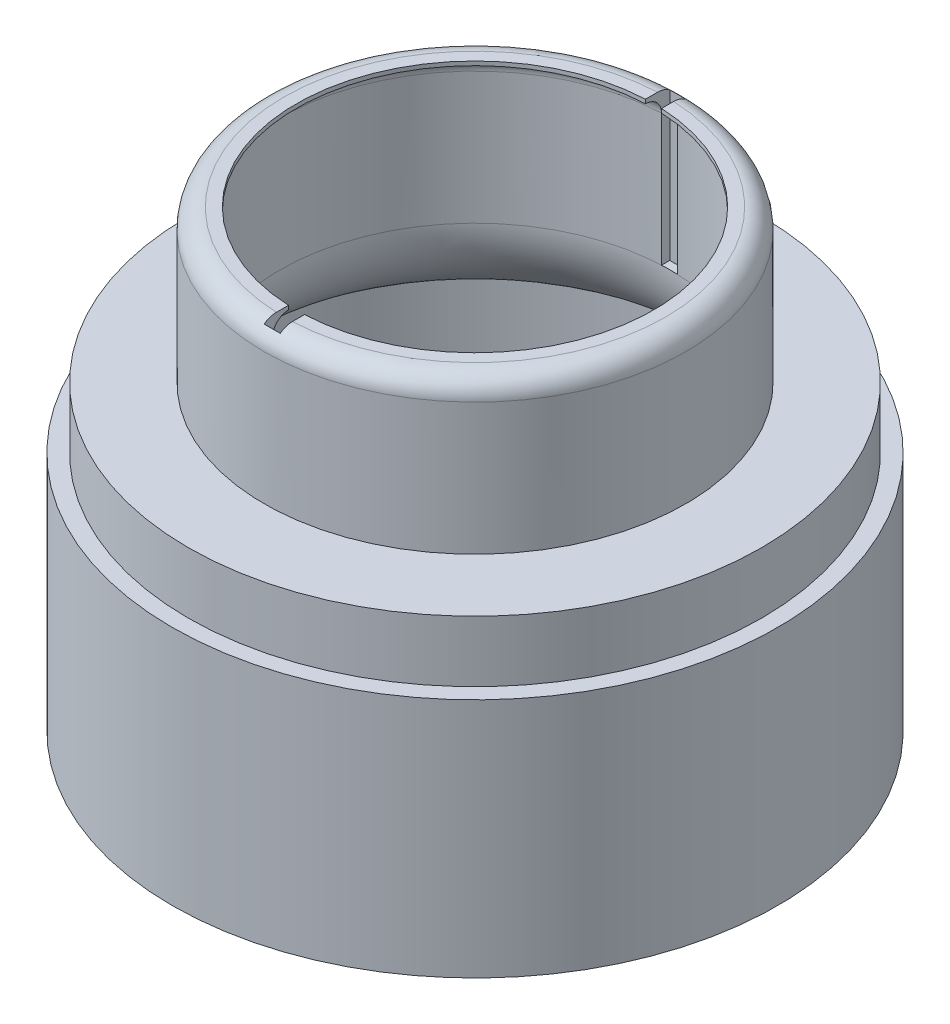
SolidWorks part; units mm, degrees
ref_plane "Front Plane" through (0, 0, 0) normal (0, 0, 1) x (1, 0, 0)
ref_plane "Top Plane" through (0, 0, 0) normal (0, 1, 0) x (1, 0, 0)
ref_plane "Right Plane" through (0, 0, 0) normal (1, 0, 0) x (0, 0, -1)
sketch "Sketch2" plane through (0, 0, 0) normal (0, 1, 0) x (1, 0, 0)
  circle A0 centre (0, 0) radius 18.85
  dimension "D1" = 37.7
extrude "Boss-Extrude1" add sketch "Sketch2" along normal blind 15
sketch "Sketch4" plane through (0, 0, 0) normal (0, -1, 0) x (-1, 0, 0)
  circle A0 centre (0, 0) radius 17.85
  dimension "D1" = 35.7
extrude "Cut-Extrude2" cut sketch "Sketch4" against normal blind 13
sketch "Sketch5" plane through (0, 15, 0) normal (0, 1, 0) x (1, 0, 0)
  circle A0 centre (0, 0) radius 13.125
  dimension "D1" = 26.25
extrude "Boss-Extrude2" add sketch "Sketch5" along normal blind 12
sketch "Sketch6" plane through (0, 27, 0) normal (0, 1, 0) x (1, 0, 0)
  circle A0 centre (0, 0) radius 12.125
  dimension "D1" = 24.25
extrude "Cut-Extrude3" cut sketch "Sketch6" against normal through all
sketch "Sketch7" plane through (0, 27, 0) normal (0, 1, 0) x (1, 0, 0)
  line L4 (0, 0) -> (0, -12.625)
  line L5 (0, 0) -> (-0.5, 0)
  line L6 (0, -12.625) -> (-0.5, -12.625)
  line L7 (-0.5, 0) -> (-0.5, -12.625)
  line L8 (0, 0) -> (0, 12.625)
  line L9 (0, 0) -> (-0.5, 0)
  line L10 (0, 12.625) -> (-0.5, 12.625)
  line L11 (-0.5, 0) -> (-0.5, 12.625)
  line L12 (0, -12.625) -> (0, 12.625)
  line L13 (0, -12.625) -> (0.5, -12.625)
  line L14 (0, 12.625) -> (0.5, 12.625)
  line L15 (0.5, -12.625) -> (0.5, 12.625)
  circle M6 centre (0, 0) radius 12.125
  dimension "D1" = 0.5
  dimension "D2" = 12.625
  dimension "D3" = 12.625
  dimension "D4" = 0.5
  dimension "D5" = 0.5
extrude "Cut-Extrude5" cut sketch "Sketch7" against normal through all and the other way blind 12 contours L11 L8 L10 M6 | L15 L14 L8 M6 | L7 L6 L4 M6 | L13 L15 L4 M6 region at (0.2509, 27, 12.3733) region at (-0.2509, 27, 12.3733) region at (-0.2509, 27, -12.3733) region at (0.2509, 27, -12.3733)
ref_plane "Plane1" through (12.125, 27, 0) normal (-1, 0, 0) x (0, 0, 1)
ref_plane "Plane2" through (0, 27, 0) normal (-1, 0, 0) x (0, 0, 1)
sketch "Sketch8" plane through (0, 27, 0) normal (-1, 0, 0) x (0, 0, 1)
  line L0 (13.125, 0) -> (-13.125, 0) construction
  line L1 (-12.1147, 0) -> (-12.625, 0) construction
  line L2 (-11.125, 1) -> (-11.125, 1.25)
  line L3 (-11.125, 1.25) -> (-11.875, 1.25)
  line L4 (-12.125, 0) -> (-13.125, 0)
  arc A0 (-13.125, 0) -> (-11.875, 1.25) centre (-11.875, 0) cw
  arc A1 (-12.125, 0) -> (-11.125, 1) centre (-11.125, 0) cw
  dimension "D1" = 1.25
  dimension "D3" = 1
  dimension "D2" = 1
ref_axis "Axis1" through (0, 13, 0) along (0, 1, 0)
revolve "Revolve3" add sketch "Sketch8" angle 360 about axis through (0, 13, 0) along (0, 1, 0)
sketch "Sketch11" plane through (0, 13, 0) normal (0, -1, 0) x (1, 0, 0)
  line L0 (0.5, -12.625) -> (-0.5, -12.625)
  line L1 (0.5, -12.625) -> (0.5, -7.625)
  line L2 (-0.5, -12.625) -> (-0.5, -7.625)
  line L3 (0.5, -7.625) -> (-0.5, -7.625)
  line L4 (0.5, 12.625) -> (-0.5, 12.625)
  line L5 (0.5, 12.625) -> (0.5, 7.625)
  line L6 (-0.5, 12.625) -> (-0.5, 7.625)
  line L7 (0.5, 7.625) -> (-0.5, 7.625)
  dimension "D1" = 5
  dimension "D2" = 5
extrude "Cut-Extrude7" cut sketch "Sketch11" against normal through all
sketch "Sketch12" plane through (0, 13, 0) normal (0, -1, 0) x (-1, 0, 0)
  circle A0 centre (0, 0) radius 12.125
  circle A1 centre (0, 0) radius 17.85
  dimension "D1" = 24.25
  dimension "D2" = 35.7
extrude "Boss-Extrude4" add sketch "Sketch12" against normal blind 5.8
fillet "Fillet3" radius 5.8 1 edges at (0, 13, -12.125)
